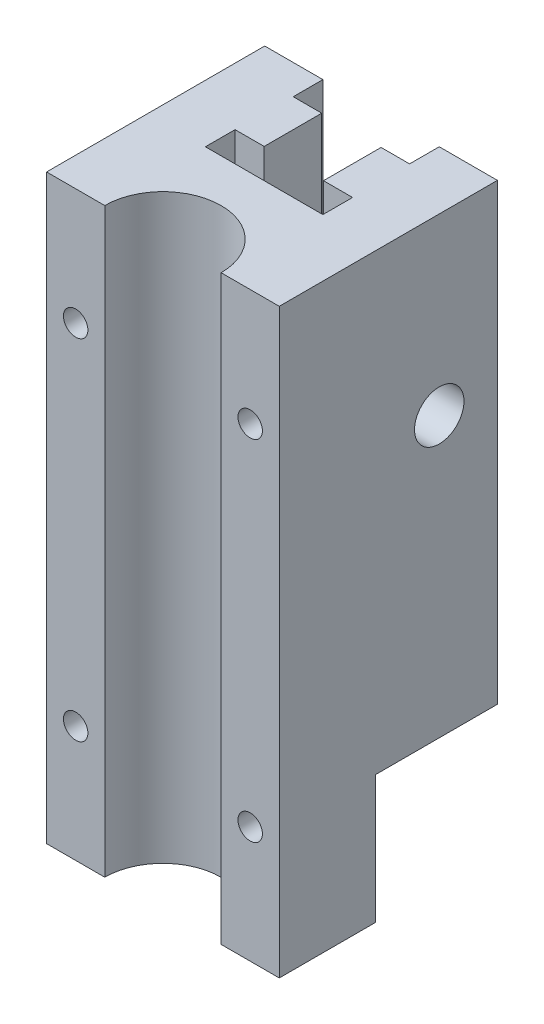
SolidWorks part; units mm, degrees
other "Markup1"
sketch "Sketch9" plane through (-20, 0, 37.5) normal (-0.6467, 0.1839, 0.7403) x (0.76, 0.0728, 0.6458)
ref_plane "Front Plane" through (0, 0, 0) normal (0, 0, 1) x (1, 0, 0)
ref_plane "Top Plane" through (0, 0, 0) normal (0, 1, 0) x (1, 0, 0)
ref_plane "Right Plane" through (0, 0, 0) normal (1, 0, 0) x (0, 0, -1)
sketch "Sketch1" plane through (0, 0, 0) normal (0, 1, 0) x (1, 0, 0)
  line L0 (10, 0) -> (-10, 0) construction
  line L1 (-10, 0) -> (-20, 0)
  line L2 (-20, 0) -> (-20, -37.5)
  line L3 (-20, -37.5) -> (20, -37.5)
  line L4 (20, -37.5) -> (20, 0)
  line L5 (20, 0) -> (10, 0)
  line L6 (10, 0) -> (10, -5.1)
  line L7 (10, -5.1) -> (5.1, -5.1)
  line L8 (5.1, -5.1) -> (5.1, -15)
  line L9 (5.1, -15) -> (10.1, -15)
  line L10 (10.1, -15) -> (10.1, -20.1)
  line L11 (10.1, -20.1) -> (-10.1, -20.1)
  line L12 (0, 0) -> (0, -20.1) construction
  line L13 (-10, 0) -> (-10, -5.1)
  line L14 (-10, -5.1) -> (-5.1, -5.1)
  line L15 (-5.1, -5.1) -> (-5.1, -15)
  line L16 (-5.1, -15) -> (-10.1, -15)
  line L17 (-10.1, -15) -> (-10.1, -20.1)
  line L18 (0, 0) -> (0, -37.5) construction
  circle A1 centre (0, -37.5) radius 10
  point P3 (0, 0)
  dimension "D10" = 20
  dimension "D1" = 37.5
  dimension "D2" = 5.1
  dimension "D3" = 4.9
  dimension "D4" = 5
  dimension "D5" = 9.9
  dimension "D6" = 5.1
  dimension "D7" = 10.1
  dimension "D8" = 40
  dimension "D9" = 20
  dimension "D11" = 37.5
extrude "Boss-Extrude1" add sketch "Sketch1" against normal blind 100 contours A1 L3 L4 L5 L6 L7 L8 L9 L10 L11 L17 L16 L15 L14 L13 L1 L2 region at (-10.5483, 0, 2.55)
sketch "Sketch5" plane through (0, -100, 0) normal (0, -1, 0) x (1, 0, 0)
  line L0 (-20, 0) -> (-20, 37.5) construction
  line L1 (20, 0) -> (-20, 0)
  line L2 (20, 0) -> (20, 21)
  line L3 (20, 21) -> (-20, 21)
  line L4 (-20, 0) -> (-20, 21)
  dimension "D1" = 21
extrude "Cut-Extrude5" cut sketch "Sketch5" against normal blind 22
sketch "Sketch3" plane through (20, 0, 0) normal (1, 0, 0) x (0, 0, -1)
  line L0 (0, -78) -> (0, 0) construction
  line L1 (0, 0) -> (-20, 0)
  line L2 (0, 0) -> (0, -25)
  line L3 (0, -25) -> (-20, -25)
  line L4 (-20, 0) -> (-20, -25)
  line L5 (-20, -25) -> (0, -25)
  line L6 (-20, -25) -> (-20, -35)
  line L7 (-20, -35) -> (0, -35)
  line L8 (0, -25) -> (0, -35)
  line L9 (-15, -25) -> (-15, -35)
  line L10 (-5, -25) -> (-5, -35)
  line L11 (-10, -25) -> (-10, -35) construction
  line L12 (-15, -30) -> (-5, -30) construction
  line L13 (-37.5, 0) -> (0, 0) construction
  circle A0 centre (-10, -30) radius 2.5
  circle A1 centre (-10, -30) radius 4.25
  dimension "D6" = 5
  dimension "D7" = 8.5
  dimension "D1" = 20
  dimension "D2" = 0
  dimension "D3" = 10
  dimension "D4" = 5
  dimension "D5" = 10
  dimension "D9" = 25
extrude "Cut-Extrude3" cut sketch "Sketch3<3>" against normal through all contours A0 region at (20, -30, 10)
sketch "Sketch3<3>" plane through (20, 0, 0) normal (1, 0, 0) x (0, 0, -1) same geometry as "Sketch3"
extrude "Cut-Extrude4" cut sketch "Sketch3" against normal blind 6 contours A1 A0 region at (20, -30, 14.1298)
sketch "Sketch7" plane through (0, 0, 37.5) normal (0, 0, 1) x (1, 0, 0)
  line L0 (-20, -100) -> (-10, -100) construction
  line L1 (-10, -100) -> (-10, 0) construction
  line L2 (10, -100) -> (20, -100) construction
  line L3 (10, -100) -> (10, 0) construction
  line L4 (20, -100) -> (20, 0) construction
  line L5 (10, 0) -> (20, 0) construction
  line L6 (-20, 0) -> (-10, 0) construction
  line L7 (-20, -100) -> (-20, 0) construction
  line L8 (-20, -100) -> (-10, -100)
  line L9 (-10, -100) -> (-10, 0)
  line L10 (10, -100) -> (20, -100)
  line L11 (10, -100) -> (10, 0)
  line L12 (20, -100) -> (20, 0)
  line L13 (10, 0) -> (20, 0)
  line L14 (-20, 0) -> (-10, 0)
  line L15 (-20, -100) -> (-20, 0)
  line L16 (0, -100) -> (0, 0) construction
  line L17 (-10, 0) -> (10, 0)
  line L18 (-10, 0) -> (-10, -100)
  line L19 (-10, -100) -> (10, -100)
  line L20 (10, 0) -> (10, -100)
  line L21 (-15, 0) -> (-15, -100) construction
  line L22 (15, 0) -> (15, -100) construction
  circle A0 centre (-15, -80) radius 2.1
  circle A1 centre (15, -80) radius 2.1
  circle A2 centre (-15, -20) radius 2.1
  circle A3 centre (15, -20) radius 2.1
  dimension "D1" = 4.2
  dimension "D2" = 4.2
  dimension "D7" = 4.2
  dimension "D8" = 4.2
  dimension "D3" = 20
  dimension "D4" = 20
  dimension "D5" = 20
  dimension "D6" = 20
extrude "Cut-Extrude7" cut sketch "Sketch7" against normal blind 10 contours A2 | A3 | A1 | A0
sketch "Sketch10" plane through (-20, 0, 0) normal (-1, 0, 0) x (0, 0, 1)
  line L1 (13.4995, -29.9388) -> (11.6967, -26.9388)
  line L2 (11.6967, -26.9388) -> (8.1972, -27)
  line L3 (8.1972, -27) -> (6.5005, -30.0612)
  line L4 (6.5005, -30.0612) -> (8.3033, -33.0612)
  line L5 (8.3033, -33.0612) -> (11.8028, -33)
  line L6 (11.8028, -33) -> (13.4995, -29.9388)
  circle A0 centre (10, -30) radius 2.5 construction
  circle A1 centre (10, -30) radius 2.5
  circle A2 centre (10, -30) radius 3.0311 construction
  point P3 (0, 0)
  point P12 (6.9696, -29.9346)
  dimension "D1" = 3.5
  dimension "D2" = 3
extrude "Cut-Extrude8" cut sketch "Sketch10" against normal blind 3
